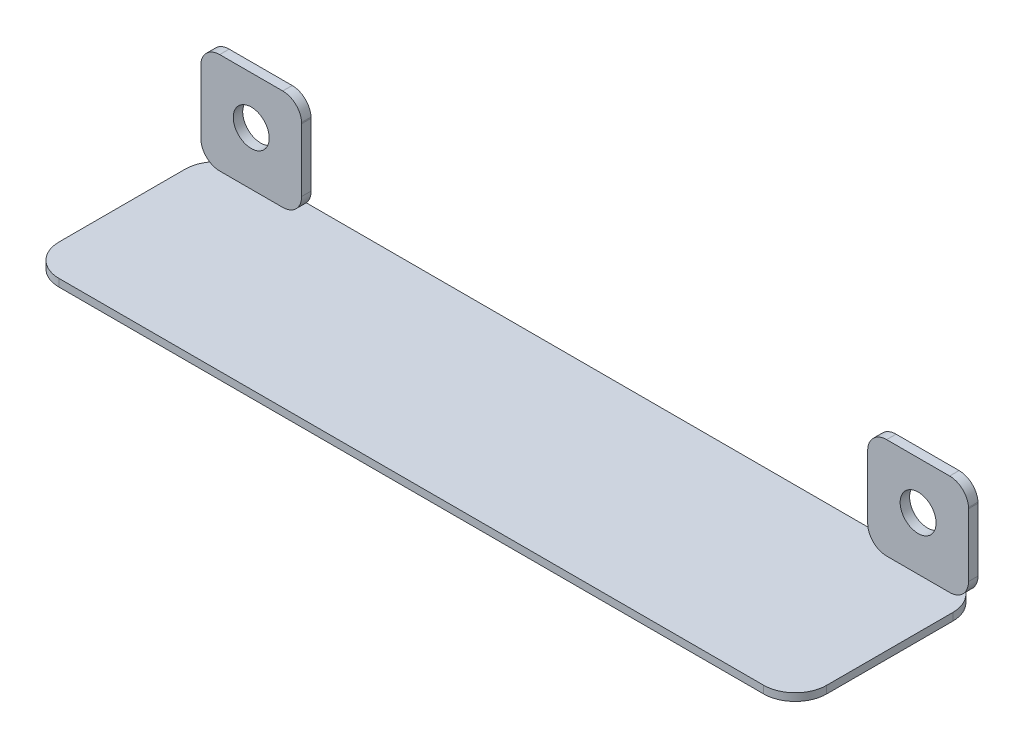
SolidWorks part; units mm, degrees
ref_plane "Front Plane" through (0, 0, 0) normal (0, 0, 1) x (1, 0, 0)
ref_plane "Top Plane" through (0, 0, 0) normal (0, 1, 0) x (1, 0, 0)
ref_plane "Right Plane" through (0, 0, 0) normal (1, 0, 0) x (0, 0, -1)
sketch "Sketch3" plane through (0, 0, 0) normal (0, 0, 1) x (1, 0, 0)
  line L6 (-7.9975, -43.2281) -> (-8, -43.4)
  line L7 (-8, -43.4) -> (-8, -53.4)
  line L8 (-5, -56.4) -> (5, -56.4)
  line L9 (8, -53.4) -> (8, -43.4)
  line L10 (8, -43.4) -> (7.9975, -43.2281)
  line L11 (5, -40.4) -> (-5, -40.4)
  line L12 (-7.9975, -43.2281) -> (-8, -43.4)
  line L13 (-8, -43.4) -> (-8, -53.4)
  line L14 (-5, -56.4) -> (5, -56.4)
  line L15 (8, -53.4) -> (8, -43.4)
  line L16 (8, -43.4) -> (7.9975, -43.2281)
  line L17 (5, -40.4) -> (-5, -40.4)
  line L18 (110.8, -40.4) -> (100.8, -40.4)
  line L19 (97.8025, -43.2281) -> (97.8, -43.4)
  line L20 (97.8, -43.4) -> (97.8, -53.4)
  line L21 (100.8, -56.4) -> (110.8, -56.4)
  line L22 (113.8, -53.4) -> (113.8, -43.4)
  line L23 (113.8, -43.4) -> (113.7975, -43.2281)
  line L24 (110.8, -40.4) -> (100.8, -40.4)
  line L25 (97.8025, -43.2281) -> (97.8, -43.4)
  line L26 (97.8, -43.4) -> (97.8, -53.4)
  line L27 (100.8, -56.4) -> (110.8, -56.4)
  line L28 (113.8, -53.4) -> (113.8, -43.4)
  line L29 (113.8, -43.4) -> (113.7975, -43.2281)
  circle A0 centre (0, -47.9524) radius 2.85 construction
  circle A1 centre (0, -47.9524) radius 2.85
  arc A2 (-5, -40.4) -> (-7.9975, -43.2281) centre (-5.0013, -43.4012) ccw
  arc A3 (-8, -53.4) -> (-5, -56.4) centre (-5, -53.4) ccw
  arc A4 (5, -56.4) -> (8, -53.4) centre (5, -53.4) ccw
  arc A5 (7.9975, -43.2281) -> (5, -40.4) centre (5.0013, -43.4012) ccw
  arc A6 (-5, -40.4) -> (-7.9975, -43.2281) centre (-5.0013, -43.4012) ccw
  arc A7 (-8, -53.4) -> (-5, -56.4) centre (-5, -53.4) ccw
  arc A8 (5, -56.4) -> (8, -53.4) centre (5, -53.4) ccw
  arc A9 (7.9975, -43.2281) -> (5, -40.4) centre (5.0013, -43.4012) ccw
  circle A10 centre (105.8, -47.9524) radius 2.85 construction
  circle A11 centre (105.8, -47.9524) radius 2.85
  arc A12 (100.8, -40.4) -> (97.8025, -43.2281) centre (100.7987, -43.4012) ccw
  arc A13 (97.8, -53.4) -> (100.8, -56.4) centre (100.8, -53.4) ccw
  arc A14 (110.8, -56.4) -> (113.8, -53.4) centre (110.8, -53.4) ccw
  arc A15 (113.7975, -43.2281) -> (110.8, -40.4) centre (110.8013, -43.4012) ccw
  arc A16 (100.8, -40.4) -> (97.8025, -43.2281) centre (100.7987, -43.4012) ccw
  arc A17 (97.8, -53.4) -> (100.8, -56.4) centre (100.8, -53.4) ccw
  arc A18 (110.8, -56.4) -> (113.8, -53.4) centre (110.8, -53.4) ccw
  arc A19 (113.7975, -43.2281) -> (110.8, -40.4) centre (110.8013, -43.4012) ccw
  dimension "D1" = 0
  dimension "D2" = 0
extrude "Boss-Extrude3" add sketch "Sketch3" along normal up to surface (1.5 mm away)
sketch "Sketch2" plane through (0, -56.4, 0) normal (0, -1, 0) x (1, 0, 0)
  line L1 (-8, -1) -> (113.8, -1)
  line L2 (-8, -1) -> (-8, 29)
  line L3 (-8, 29) -> (113.8, 29)
  line L4 (113.8, -1) -> (113.8, 29)
  line L5 (113.8, 0) -> (113.8, -78.8637) construction
  line L6 (-8, -78.8637) -> (-8, 0) construction
  line L9 (-5, 0) -> (-8, 0) construction
  point P4 (-8, 32.026)
  point P5 (-8, 0)
  point P6 (-8, -2.0316)
  dimension "D1" = 30
  dimension "D2" = 121.8
  dimension "D3" = 1
extrude "Boss-Extrude2" add sketch "Sketch2" along normal blind 1.2
fillet "Fillet1" radius 5 4 edges at (113.8, -57, 29) (113.8, -57, -1) (-8, -57, -1) (-8, -57, 29)
